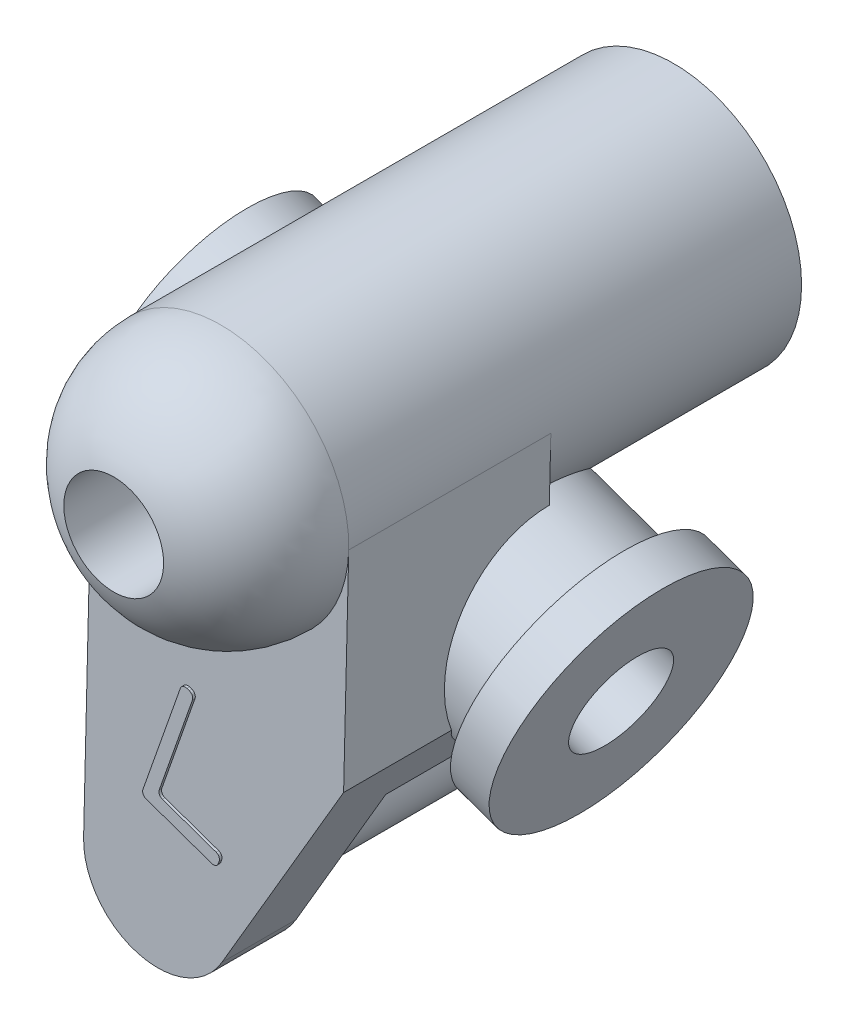
SolidWorks part; units mm, degrees
ref_plane "Plan de face" through (0, 0, 0) normal (0, 0, 1) x (1, 0, 0)
ref_plane "Plan de dessus" through (0, 0, 0) normal (0, 1, 0) x (1, 0, 0)
ref_plane "Plan de droite" through (0, 0, 0) normal (1, 0, 0) x (0, 0, -1)
sketch "Esquisse1" plane through (0, 0, 0) normal (0, 0, 1) x (1, 0, 0)
  line L0 (-2.4993, 0.0604) -> (-2.6825, -7.5149)
  line L1 (2.4993, -0.0604) -> (2.3988, -4.216)
  line L2 (2.3988, -4.216) -> (0.0185, -8.2825)
  arc A0 (2.4993, -0.0604) -> (-2.4993, 0.0604) centre (0, 0) ccw
  arc A1 (-2.6825, -7.5149) -> (0.0185, -8.2825) centre (-1.2329, -7.55) ccw
  dimension "D1" = 5
  dimension "D2" = 2.9
  dimension "D3" = 7.55
  dimension "D4" = 4.2
  dimension "D5" = 7.65
extrude "Boss.-Extru.1" add sketch "Esquisse1" along normal blind 1.45
sketch "Esquisse2" plane through (0, 0, 1.45) normal (0, 0, 1) x (1, 0, 0)
  circle A0 centre (0, 0) radius 2.5
  arc A1 (2.4993, -0.0604) -> (-2.4993, 0.0604) centre (0, 0) ccw construction
extrude "Boss.-Extru.2" add sketch "Esquisse2" along normal blind 2.2
sketch "Esquisse4" plane through (0, 0, 0) normal (0, 0, -1) x (-1, 0, 0)
  circle A0 centre (0, 0) radius 2.5
  circle A1 centre (0, 0) radius 2.5 construction
extrude "Boss.-Extru.3" add sketch "Esquisse4" along normal blind 11.05 from surface starting at face at (2.5, 0, 3.65)
sketch "Esquisse5" plane through (0, 0, 0) normal (0, 0, -1) x (-1, 0, 0)
  circle A0 centre (1.2329, -7.55) radius 0.95
  dimension "D1" = 1.9
extrude "Boss.-Extru.4" add sketch "Esquisse5" along normal blind 7.5 from surface starting at face at (-0.6041, -3.8578, 1.45)
fillet "Congé2" radius 2.2 1 edges at (2.5, 0, 3.65)
ref_plane "Plan1" through (-2.3583, 0.8298, 0) normal (-0.9433, 0.3319, 0) x (0, 0, 1)
sketch "Esquisse6" plane through (-2.3583, 0.8298, 0) normal (-0.9433, 0.3319, 0) x (0, 0, 1)
  line L0 (-7.4, 2.5) -> (-7.4, -2.5) construction
  line L1 (1.45, 2.5) -> (-7.4, 2.5) construction
  line L2 (-2.5, -4.4) -> (0, -4.4)
  line L3 (0, -0.7725) -> (0, -7.9793) construction
  line L4 (-2.5, -0.4) -> (-2.5, 1.2979)
  line L5 (-2.5, 1.2979) -> (0, 1.2979)
  line L6 (0, 1.2979) -> (0, -4.4)
  arc A0 (-2.5, -0.4) -> (-2.5, -4.4) centre (-2.5, -2.4) ccw
  dimension "D1" = 4
  dimension "D2" = 4.9
  dimension "D3" = 4.9
extrude "Boss.-Extru.5" add sketch "Esquisse6" along normal blind 1 and the other way blind 7.45
sketch "Esquisse13" plane through (0, 0, 0) normal (0, 0, 1) x (1, 0, 0)
  line L0 (-1.5848, 1.9335) -> (-2.8708, 2.386)
  line L1 (-2.8708, 2.386) -> (-4.762, -2.9888)
  line L2 (-4.762, -2.9888) -> (-2.5915, -3.7526)
  line L3 (-2.5915, -3.7526) -> (-2.4993, 0.0604)
  line L4 (1.7715, -5.2878) -> (3.2089, -5.7936)
  line L5 (3.2089, -5.7936) -> (5.1002, -0.4187)
  line L6 (5.1002, -0.4187) -> (2.4464, 0.5151)
  line L7 (2.4993, -0.0604) -> (2.3988, -4.216)
  line L8 (2.3988, -4.216) -> (1.7715, -5.2878)
  arc A0 (-2.4993, 0.0604) -> (-1.5848, 1.9335) centre (0, 0) cw
  arc A1 (2.4464, 0.5151) -> (2.4993, -0.0604) centre (0, 0) cw
extrude "Enlèv. mat.-Extru.7" cut sketch "Esquisse13" against normal blind 5.4
sketch "Esquisse14" plane through (-2.3583, 0.8298, 0) normal (-0.9433, 0.3319, 0) x (0, 0, 1)
  circle A0 centre (-2.5, -2.4) radius 2
  arc A1 (-3.6625, -0.7725) -> (-2.5, -4.4) centre (-2.5, -2.4) ccw construction
extrude "Boss.-Extru.14" add sketch "Esquisse14" along normal blind 1 and the other way blind 7.45
sketch "Esquisse15" plane through (4.6694, -1.643, 0) normal (0.9433, -0.3319, 0) x (0, 0, -1)
  circle A0 centre (2.5, -2.4) radius 2.45
  dimension "D1" = 4.9
extrude "Boss.-Extru.15" add sketch "Esquisse15" against normal blind 0.8
sketch "Esquisse16" plane through (0, 0, -6.05) normal (0, 0, -1) x (-1, 0, 0)
  circle A0 centre (1.2329, -7.55) radius 3.6
  circle A1 centre (1.2329, -7.55) radius 0.95
  circle A2 centre (1.2329, -7.55) radius 0.95 construction
  dimension "D1" = 7.2
extrude "Enlèv. mat.-Extru.9" cut sketch "Esquisse16" against normal up to surface (6.05 mm away) up to face at (-0.2829, -7.55, 0)
sketch "Esquisse17" plane through (0, 0, -7.4) normal (0, 0, -1) x (-1, 0, 0)
  circle A0 centre (0, 0) radius 0.975
  dimension "D1" = 1.95
extrude "Enlèv. mat.-Extru.10" cut sketch "Esquisse17" against normal blind 12.8
sketch "Esquisse18" plane through (4.6694, -1.643, 0) normal (0.9433, -0.3319, 0) x (0, 0, -1)
  circle A0 centre (2.5, -2.4) radius 0.975
  dimension "D1" = 1.95
extrude "Enlèv. mat.-Extru.11" cut sketch "Esquisse18" against normal blind 12.8
sketch "Esquisse19" plane through (0, 0, 1.45) normal (0, 0, 1) x (1, 0, 0)
  line L0 (-0.7411, -3.9948) -> (-1.4732, -6.0753)
  line L1 (-1.4121, -6.2028) -> (-0.1275, -6.6548)
  line L2 (0, -6.5937) -> (0.0166, -6.5465)
  line L3 (-0.0445, -6.419) -> (-1.0933, -6.05)
  line L4 (-1.1544, -5.9224) -> (-0.5053, -4.0777)
  line L5 (-0.5665, -3.9502) -> (-0.6136, -3.9336)
  line L6 (-4.762, -2.9888) -> (-2.5915, -3.7526) construction
  line L7 (-3.4343, 0.7844) -> (-4.762, -2.9888) construction
  arc A0 (-1.0933, -6.05) -> (-1.1544, -5.9224) centre (-1.0601, -5.9556) cw
  arc A1 (-1.4732, -6.0753) -> (-1.4121, -6.2028) centre (-1.3789, -6.1085) ccw
  arc A2 (-0.1275, -6.6548) -> (0, -6.5937) centre (-0.0943, -6.5605) ccw
  arc A3 (0.0166, -6.5465) -> (-0.0445, -6.419) centre (-0.0777, -6.5133) ccw
  arc A4 (-0.5053, -4.0777) -> (-0.5665, -3.9502) centre (-0.5996, -4.0445) ccw
  arc A5 (-0.7411, -3.9948) -> (-0.6136, -3.9336) centre (-0.6468, -4.0279) cw
  point P16 (-0.0332, -6.688)
  point P19 (0.0498, -6.4522)
  point P22 (-0.4721, -3.9834)
  point P25 (-0.708, -3.9004)
  dimension "D3" = 0.1
  dimension "D1" = 0.25
  dimension "D2" = 0.25
  dimension "D4" = 2.2056
  dimension "D5" = 1.3618
extrude "Boss.-Extru.16" add sketch "Esquisse19" along normal blind 0.05
scale "Scale1" scale about centroid uniform scaling yes scale factor 6.5
